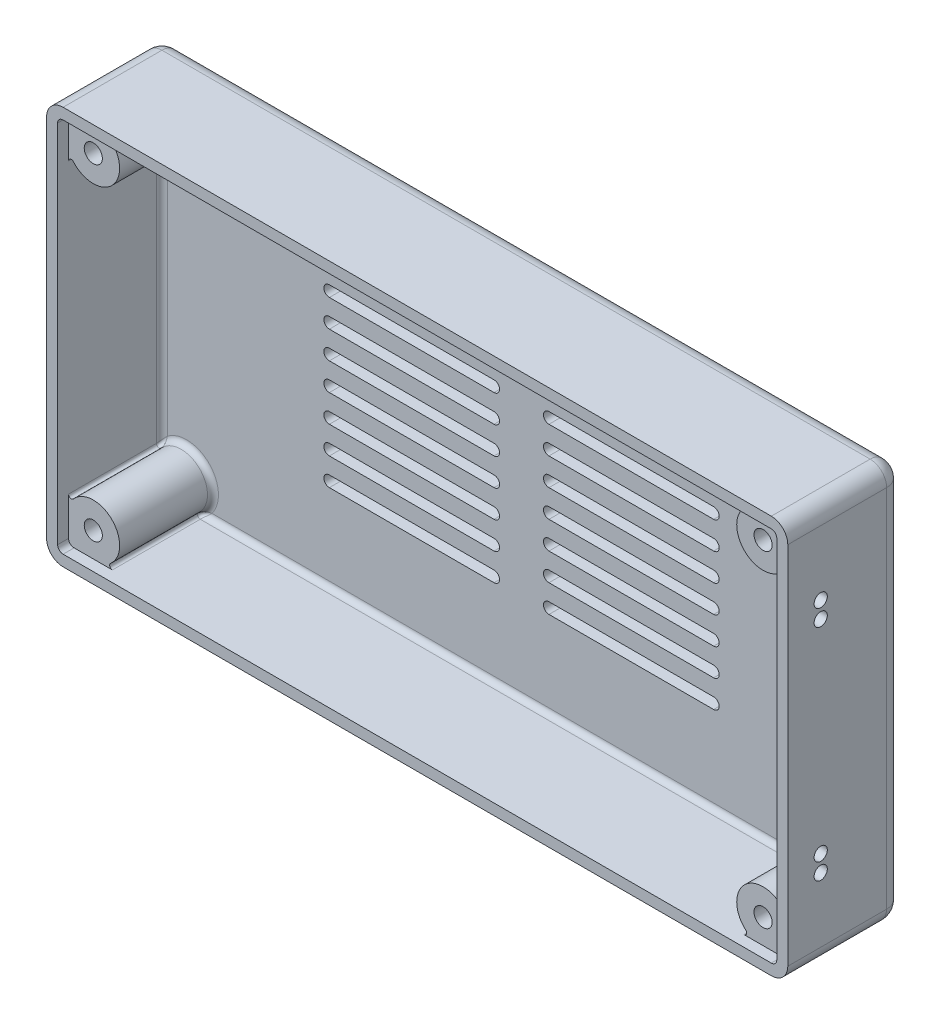
SolidWorks part; units mm, degrees
ref_plane "Front Plane" through (0, 0, 0) normal (0, 0, 1) x (1, 0, 0)
ref_plane "Top Plane" through (0, 0, 0) normal (0, 1, 0) x (1, 0, 0)
ref_plane "Right Plane" through (0, 0, 0) normal (1, 0, 0) x (0, 0, -1)
sketch "Sketch1" plane through (0, 0, 0) normal (0, 0, 1) x (1, 0, 0)
  line L0 (32.5, 18.75) -> (62.5, 18.75) construction
  line L1 (3, 0) -> (132, 0)
  line L2 (0, 3) -> (0, 69.5)
  line L3 (3, 72.5) -> (132, 72.5)
  line L4 (135, 3) -> (135, 69.5)
  line L5 (32.5, 19.75) -> (62.5, 19.75)
  line L6 (32.5, 17.75) -> (62.5, 17.75)
  line L8 (72.5, 18.75) -> (102.5, 18.75) construction
  line L9 (72.5, 19.75) -> (102.5, 19.75)
  line L10 (72.5, 17.75) -> (102.5, 17.75)
  line L12 (32.5, 23.75) -> (62.5, 23.75) construction
  line L13 (32.5, 24.75) -> (62.5, 24.75)
  line L14 (32.5, 22.75) -> (62.5, 22.75)
  line L16 (72.5, 23.75) -> (102.5, 23.75) construction
  line L17 (72.5, 24.75) -> (102.5, 24.75)
  line L18 (72.5, 22.75) -> (102.5, 22.75)
  line L25 (32.5, 28.75) -> (62.5, 28.75) construction
  line L26 (32.5, 29.75) -> (62.5, 29.75)
  line L27 (32.5, 27.75) -> (62.5, 27.75)
  line L29 (72.5, 28.75) -> (102.5, 28.75) construction
  line L30 (72.5, 29.75) -> (102.5, 29.75)
  line L31 (72.5, 27.75) -> (102.5, 27.75)
  line L32 (32.5, 33.75) -> (62.5, 33.75) construction
  line L33 (32.5, 34.75) -> (62.5, 34.75)
  line L34 (32.5, 32.75) -> (62.5, 32.75)
  line L36 (72.5, 33.75) -> (102.5, 33.75) construction
  line L37 (72.5, 34.75) -> (102.5, 34.75)
  line L38 (72.5, 32.75) -> (102.5, 32.75)
  line L39 (32.5, 38.75) -> (62.5, 38.75) construction
  line L40 (32.5, 39.75) -> (62.5, 39.75)
  line L41 (32.5, 37.75) -> (62.5, 37.75)
  line L43 (72.5, 38.75) -> (102.5, 38.75) construction
  line L44 (72.5, 39.75) -> (102.5, 39.75)
  line L45 (72.5, 37.75) -> (102.5, 37.75)
  line L46 (32.5, 43.75) -> (62.5, 43.75) construction
  line L47 (32.5, 44.75) -> (62.5, 44.75)
  line L48 (32.5, 42.75) -> (62.5, 42.75)
  line L50 (72.5, 43.75) -> (102.5, 43.75) construction
  line L51 (72.5, 44.75) -> (102.5, 44.75)
  line L52 (72.5, 42.75) -> (102.5, 42.75)
  line L53 (32.5, 48.75) -> (62.5, 48.75) construction
  line L54 (32.5, 49.75) -> (62.5, 49.75)
  line L55 (32.5, 47.75) -> (62.5, 47.75)
  line L57 (72.5, 48.75) -> (102.5, 48.75) construction
  line L58 (72.5, 49.75) -> (102.5, 49.75)
  line L59 (72.5, 47.75) -> (102.5, 47.75)
  line L60 (32.5, 53.75) -> (62.5, 53.75) construction
  line L61 (32.5, 54.75) -> (62.5, 54.75)
  line L62 (32.5, 52.75) -> (62.5, 52.75)
  line L64 (72.5, 53.75) -> (102.5, 53.75) construction
  line L65 (72.5, 54.75) -> (102.5, 54.75)
  line L66 (72.5, 52.75) -> (102.5, 52.75)
  arc A0 (132, 0) -> (135, 3) centre (132, 3) ccw
  arc A1 (132, 72.5) -> (135, 69.5) centre (132, 69.5) cw
  arc A2 (0, 69.5) -> (3, 72.5) centre (3, 69.5) cw
  arc A3 (3, 0) -> (0, 3) centre (3, 3) cw
  circle A4 centre (6.5, 66) radius 1.65
  circle A5 centre (128.5, 6.5) radius 1.65
  circle A6 centre (128.5, 66) radius 1.65
  circle A7 centre (6.5, 6.5) radius 1.65
  arc A8 (32.5, 19.75) -> (32.5, 17.75) centre (32.5, 18.75) ccw
  arc A9 (62.5, 17.75) -> (62.5, 19.75) centre (62.5, 18.75) ccw
  arc A10 (72.5, 19.75) -> (72.5, 17.75) centre (72.5, 18.75) ccw
  arc A11 (102.5, 17.75) -> (102.5, 19.75) centre (102.5, 18.75) ccw
  arc A12 (32.5, 24.75) -> (32.5, 22.75) centre (32.5, 23.75) ccw
  arc A13 (62.5, 22.75) -> (62.5, 24.75) centre (62.5, 23.75) ccw
  arc A14 (72.5, 24.75) -> (72.5, 22.75) centre (72.5, 23.75) ccw
  arc A15 (102.5, 22.75) -> (102.5, 24.75) centre (102.5, 23.75) ccw
  arc A16 (32.5, 29.75) -> (32.5, 27.75) centre (32.5, 28.75) ccw
  arc A17 (62.5, 27.75) -> (62.5, 29.75) centre (62.5, 28.75) ccw
  arc A18 (72.5, 29.75) -> (72.5, 27.75) centre (72.5, 28.75) ccw
  arc A19 (102.5, 27.75) -> (102.5, 29.75) centre (102.5, 28.75) ccw
  arc A20 (32.5, 34.75) -> (32.5, 32.75) centre (32.5, 33.75) ccw
  arc A21 (62.5, 32.75) -> (62.5, 34.75) centre (62.5, 33.75) ccw
  arc A22 (72.5, 34.75) -> (72.5, 32.75) centre (72.5, 33.75) ccw
  arc A23 (102.5, 32.75) -> (102.5, 34.75) centre (102.5, 33.75) ccw
  arc A24 (32.5, 39.75) -> (32.5, 37.75) centre (32.5, 38.75) ccw
  arc A25 (62.5, 37.75) -> (62.5, 39.75) centre (62.5, 38.75) ccw
  arc A26 (72.5, 39.75) -> (72.5, 37.75) centre (72.5, 38.75) ccw
  arc A27 (102.5, 37.75) -> (102.5, 39.75) centre (102.5, 38.75) ccw
  arc A28 (32.5, 44.75) -> (32.5, 42.75) centre (32.5, 43.75) ccw
  arc A29 (62.5, 42.75) -> (62.5, 44.75) centre (62.5, 43.75) ccw
  arc A30 (72.5, 44.75) -> (72.5, 42.75) centre (72.5, 43.75) ccw
  arc A31 (102.5, 42.75) -> (102.5, 44.75) centre (102.5, 43.75) ccw
  arc A32 (32.5, 49.75) -> (32.5, 47.75) centre (32.5, 48.75) ccw
  arc A33 (62.5, 47.75) -> (62.5, 49.75) centre (62.5, 48.75) ccw
  arc A34 (72.5, 49.75) -> (72.5, 47.75) centre (72.5, 48.75) ccw
  arc A35 (102.5, 47.75) -> (102.5, 49.75) centre (102.5, 48.75) ccw
  arc A36 (32.5, 54.75) -> (32.5, 52.75) centre (32.5, 53.75) ccw
  arc A37 (62.5, 52.75) -> (62.5, 54.75) centre (62.5, 53.75) ccw
  arc A38 (72.5, 54.75) -> (72.5, 52.75) centre (72.5, 53.75) ccw
  arc A39 (102.5, 52.75) -> (102.5, 54.75) centre (102.5, 53.75) ccw
  point P13 (47.5, 18.75)
  point P30 (87.5, 18.75)
  point P39 (47.5, 23.75)
  point P48 (87.5, 23.75)
  point P60 (47.5, 28.75)
  point P70 (87.5, 28.75)
  point P77 (47.5, 33.75)
  point P86 (87.5, 33.75)
  point P93 (47.5, 38.75)
  point P102 (87.5, 38.75)
  point P109 (47.5, 43.75)
  point P118 (87.5, 43.75)
  point P125 (47.5, 48.75)
  point P134 (87.5, 48.75)
  point P141 (47.5, 53.75)
  point P150 (87.5, 53.75)
extrude "Boss-Extrude1" add sketch "Sketch1" along normal blind 21
sketch "Sketch2" plane through (0, 0, 21) normal (0, 0, 1) x (1, 0, 0)
  line L2 (9.9771, 70.5) -> (125.0229, 70.5)
  line L4 (2, 62.5229) -> (2, 9.9771)
  line L5 (9.9771, 2) -> (125.0229, 2)
  line L6 (133, 62.5229) -> (133, 9.9771)
  arc A0 (2.8774, 62.851) -> (9.649, 69.6226) centre (6.5, 66) ccw
  arc A1 (132.1226, 9.649) -> (125.351, 2.8774) centre (128.5, 6.5) ccw
  arc A2 (125.351, 69.6226) -> (132.1226, 62.851) centre (128.5, 66) ccw
  arc A3 (9.649, 2.8774) -> (2.8774, 9.649) centre (6.5, 6.5) ccw
  arc A4 (133, 9.9771) -> (132.1226, 9.649) centre (132.5, 9.9771) cw
  arc A5 (125.0229, 2) -> (125.351, 2.8774) centre (125.0229, 2.5) ccw
  arc A6 (132.1226, 62.851) -> (133, 62.5229) centre (132.5, 62.5229) cw
  arc A7 (125.351, 69.6226) -> (125.0229, 70.5) centre (125.0229, 70) ccw
  arc A8 (9.649, 69.6226) -> (9.9771, 70.5) centre (9.9771, 70) cw
  arc A9 (2.8774, 62.851) -> (2, 62.5229) centre (2.5, 62.5229) ccw
  arc A10 (9.9771, 2) -> (9.649, 2.8774) centre (9.9771, 2.5) cw
  arc A11 (2.8774, 9.649) -> (2, 9.9771) centre (2.5, 9.9771) cw
extrude "Cut-Extrude1" cut sketch "Sketch2" against normal offset from surface (19 mm away) 2 up to face at (47.5, 53.75, 0)
sketch "Sketch3" plane through (0, 0, 21) normal (0, 0, 1) x (1, 0, 0)
  line L5 (132, 2) -> (3, 2)
  line L6 (133, 3) -> (133, 69.5)
  line L7 (132, 70.5) -> (3, 70.5)
  line L8 (2, 3) -> (2, 69.5)
  arc A0 (133, 3) -> (132, 2) centre (132, 3) cw
  arc A1 (133, 69.5) -> (132, 70.5) centre (132, 69.5) ccw
  arc A2 (3, 2) -> (2, 3) centre (3, 3) cw
  arc A3 (2, 69.5) -> (3, 70.5) centre (3, 69.5) cw
extrude "Cut-Extrude2" cut sketch "Sketch3" against normal blind 2
fillet "Fillet1" radius 1 16 edges at (9.5087, 70.1751, 2) (9.8941, 62.6059, 2) (2.3249, 62.9913, 2) (2, 36.25, 2) (2.3249, 9.5087, 2) (9.8941, 9.8941, 2) (9.5087, 2.3249, 2) (67.5, 2, 2) (125.4913, 2.3249, 2) (125.1059, 9.8941, 2) (132.6751, 9.5087, 2) (133, 36.25, 2) (132.6751, 62.9913, 2) (125.1059, 62.6059, 2) (125.4913, 70.1751, 2) (67.5, 70.5, 2)
fillet "Fillet2" radius 3 8 edges at (134.1213, 71.6213, 0) (135, 36.25, 0) (134.1213, 0.8787, 0) (67.5, 0, 0) (0.8787, 0.8787, 0) (0, 36.25, 0) (0.8787, 71.6213, 0) (67.5, 72.5, 0)
sketch "Sketch4" plane through (0, 0, 0) normal (0, 0, -1) x (-1, 0, 0)
  line L1 (-125.2668, 66) -> (-126.8834, 68.8)
  line L2 (-126.8834, 68.8) -> (-130.1166, 68.8)
  line L3 (-130.1166, 68.8) -> (-131.7332, 66)
  line L4 (-131.7332, 66) -> (-130.1166, 63.2)
  line L5 (-130.1166, 63.2) -> (-126.8834, 63.2)
  line L6 (-126.8834, 63.2) -> (-125.2668, 66)
  line L7 (-125.2668, 6.5) -> (-126.8834, 9.3)
  line L8 (-126.8834, 9.3) -> (-130.1166, 9.3)
  line L9 (-130.1166, 9.3) -> (-131.7332, 6.5)
  line L10 (-131.7332, 6.5) -> (-130.1166, 3.7)
  line L11 (-130.1166, 3.7) -> (-126.8834, 3.7)
  line L12 (-126.8834, 3.7) -> (-125.2668, 6.5)
  line L13 (-9.7332, 66) -> (-8.1166, 63.2)
  line L14 (-8.1166, 63.2) -> (-4.8834, 63.2)
  line L15 (-4.8834, 63.2) -> (-3.2668, 66)
  line L16 (-3.2668, 66) -> (-4.8834, 68.8)
  line L17 (-4.8834, 68.8) -> (-8.1166, 68.8)
  line L18 (-8.1166, 68.8) -> (-9.7332, 66)
  line L19 (-9.7332, 6.5) -> (-8.1166, 3.7)
  line L20 (-8.1166, 3.7) -> (-4.8834, 3.7)
  line L21 (-4.8834, 3.7) -> (-3.2668, 6.5)
  line L22 (-3.2668, 6.5) -> (-4.8834, 9.3)
  line L23 (-4.8834, 9.3) -> (-8.1166, 9.3)
  line L24 (-8.1166, 9.3) -> (-9.7332, 6.5)
  circle A0 centre (-128.5, 66) radius 2.8 construction
  circle A1 centre (-128.5, 6.5) radius 2.8 construction
  circle A2 centre (-6.5, 66) radius 2.8 construction
  circle A3 centre (-6.5, 6.5) radius 2.8 construction
extrude "Cut-Extrude3" cut sketch "Sketch4" against normal offset from surface (15 mm away) 4 up to face at (126.85, 6.5, 19)
sketch "Sketch5" plane through (135, 0, 0) normal (1, 0, 0) x (0, 0, -1)
  circle A0 centre (-15, 57.75) radius 1.2
  circle A1 centre (-15, 54.75) radius 1.2
  circle A2 centre (-15, 17.75) radius 1.2
  circle A3 centre (-15, 14.75) radius 1.2
extrude "Cut-Extrude4" cut sketch "Sketch5" against normal up to surface (2 mm away) up to face at (133, 36.25, 15.5)
